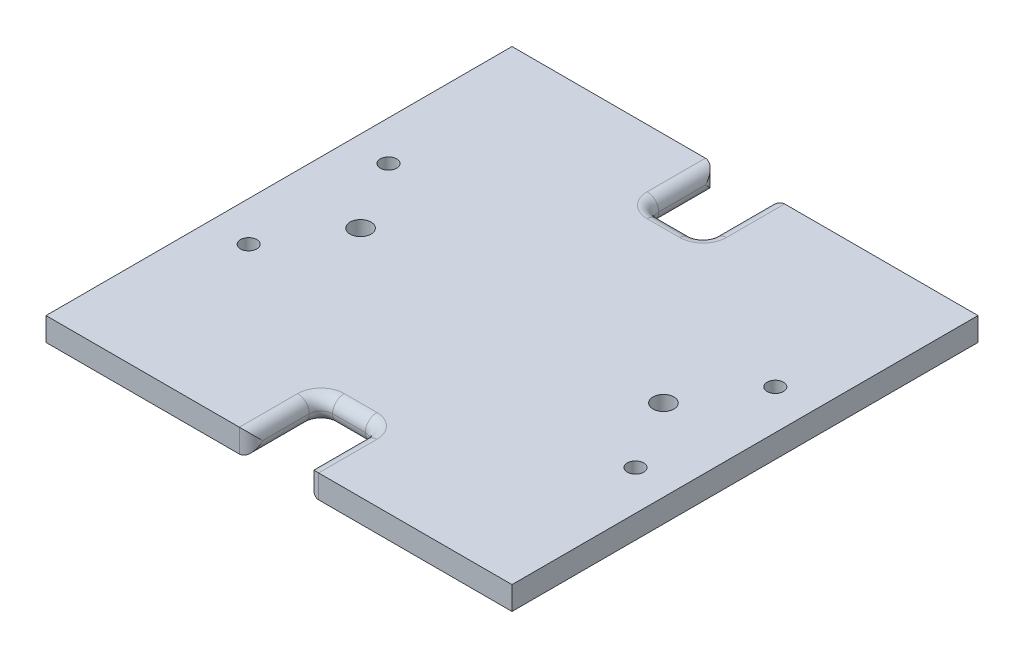
SolidWorks part; units mm, degrees
note: The reader was unsure of these and kept them because the rebuilt part matched: shared geometry of "Sketch4<4>", "Sketch4<6>".
ref_plane "Ön Düzlem" through (0, 0, 0) normal (0, 0, 1) x (1, 0, 0)
ref_plane "Üst Düzlem" through (0, 0, 0) normal (0, 1, 0) x (1, 0, 0)
ref_plane "Sağ Düzlem" through (0, 0, 0) normal (1, 0, 0) x (0, 0, -1)
sketch "Sketch1" plane through (0, 0, 0) normal (0, 0, 1) x (1, 0, 0)
  line L1 (-15.6006, 140) -> (-10.6006, 140)
  line L2 (-15.6006, 140) -> (-15.6006, 0)
  line L3 (-15.6006, 0) -> (-10.6006, 0)
  line L4 (-10.6006, 140) -> (-10.6006, 0)
  line L5 (-15.6006, 140) -> (-10.6006, 0) construction
  line L6 (-15.6006, 0) -> (-10.6006, 140) construction
  line L7 (-15.6006, 0) -> (94.3994, 0)
  line L8 (-15.6006, 0) -> (-15.6006, -5)
  line L9 (-15.6006, -5) -> (94.3994, -5)
  line L10 (94.3994, 0) -> (94.3994, -5)
  line L11 (94.3994, 0) -> (89.3994, 0)
  line L12 (94.3994, 0) -> (94.3994, 140)
  line L13 (94.3994, 140) -> (89.3994, 140)
  line L14 (89.3994, 0) -> (89.3994, 140)
  point P0 (-13.1006, 70)
  dimension "D1" = 5
  dimension "D2" = 140
  dimension "D3" = 5
  dimension "D4" = 110
  dimension "D5" = 5
extrude "Boss-Extrude1" add sketch "Sketch1" against normal blind 100 contours L10 L7 L3 L8 L9 | L14 L7 L12 L13
sketch "Sketch4" plane through (89.3994, 0, 0) normal (-1, 0, 0) x (0, 0, 1)
  line L0 (0, 0) -> (0, 45)
  line L1 (0, 0) -> (0, 140) construction
  line L2 (0, 45) -> (-100, 45)
  line L3 (-100, 0) -> (-100, 140) construction
  line L4 (-50, 45) -> (-82.05, 45)
  line L5 (-50, 45) -> (-17.95, 45)
  circle A0 centre (-50, 45) radius 9.85
  circle A1 centre (-82.05, 45) radius 9.85
  circle A2 centre (-17.95, 45) radius 9.85
  circle A3 centre (-82.05, 45) radius 7
  circle A4 centre (-50, 45) radius 7
  circle A5 centre (-17.95, 45) radius 7
  dimension "D4" = 19.7
  dimension "D5" = 19.7
  dimension "D6" = 19.7
  dimension "D7" = 14
  dimension "D8" = 14
  dimension "D9" = 14
  dimension "D1" = 45
  dimension "D2" = 32.05
  dimension "D3" = 32.05
extrude "Cut-Extrude3" cut sketch "Sketch4" along normal through all both and the other way through all contours L2 A3 L4 | L4 A3 L2 | L2 A4 | L2 A4 | L2 A5 | L2 A5
extrude "Cut-Extrude4" cut sketch "Sketch4<4>" against normal blind 3
sketch "Sketch4<4>" plane through (89.3994, 0, 0) normal (-1, 0, 0) x (0, 0, 1) same geometry as "Sketch4"
extrude "Cut-Extrude5" cut sketch "Sketch4<6>" along normal blind 103
sketch "Sketch4<6>" plane through (89.3994, 0, 0) normal (-1, 0, 0) x (0, 0, 1) same geometry as "Sketch4"
sketch "Sketch5" plane through (-15.6006, 0, 0) normal (-1, 0, 0) x (0, 0, 1)
  line L0 (0, 140) -> (0, 119.5)
  line L1 (0, 140) -> (0, -5) construction
  line L2 (0, 119.5) -> (-21.25, 119.5)
  line L3 (-100, 140) -> (-100, 119.5)
  line L4 (-100, 140) -> (-100, -5) construction
  line L5 (-100, 119.5) -> (-78.75, 119.5)
  circle A0 centre (-78.75, 119.5) radius 2.25
  circle A1 centre (-21.25, 119.5) radius 2.25
  dimension "D4" = 4.5
  dimension "D5" = 4.5
  dimension "D1" = 20.5
  dimension "D2" = 21.25
  dimension "D3" = 21.25
extrude "Cut-Extrude6" cut sketch "Sketch5" against normal up to next and the other way through all
sketch "Sketch6" plane through (0, -5, 0) normal (0, -1, 0) x (1, 0, 0)
  line L0 (39.3994, -50) -> (71.8994, -50)
  line L1 (39.3994, -50) -> (6.8994, -50)
  circle A0 centre (71.8994, -50) radius 2.25
  circle A1 centre (6.8994, -50) radius 2.25
  dimension "D3" = 4.5
  dimension "D4" = 4.5
  dimension "D1" = 32.5
  dimension "D2" = 32.5
extrude "Cut-Extrude7" cut sketch "Sketch6" against normal up to next
sketch "Sketch7" plane through (0, 0, 0) normal (0, 1, 0) x (1, 0, 0)
  line L0 (39.3994, 100) -> (33.3994, 100)
  line L1 (-10.6006, 100) -> (89.3994, 100) construction
  line L2 (33.3994, 100) -> (45.3994, 100)
  line L3 (9.1494, 50) -> (69.6494, 50)
  line L4 (33.3994, 100) -> (45.3994, 100)
  line L5 (33.3994, 100) -> (33.3994, 85)
  line L6 (33.3994, 85) -> (45.3994, 85)
  line L7 (45.3994, 100) -> (45.3994, 85)
  line L8 (33.3994, 0) -> (45.3994, 0)
  line L9 (33.3994, 15) -> (45.3994, 15)
  line L10 (45.3994, 0) -> (45.3994, 15)
  line L11 (33.3994, 0) -> (33.3994, 15)
  circle A0 centre (6.8994, 50) radius 2.25 construction
  circle A1 centre (71.8994, 50) radius 2.25 construction
  line M10 (-10.6006, 0) -> (89.3994, 0)
  line M12 (89.3994, 100) -> (-10.6006, 100)
  dimension "D1" = 6
  dimension "D2" = 12
  dimension "D3" = 15
extrude "Cut-Extrude8" cut sketch "Sketch7" against normal through all contours L7 L5 L6 M12 | L11 L10 L9 M10
fillet "Fillet3" radius 2.5 8 edges at (45.3994, -2.5, 0) (45.3994, -5, -7.5) (45.3994, 0, -7.5) (39.3994, -5, -15) (39.3994, 0, -15) (33.3994, -5, -7.5) (33.3994, -2.5, 0) (33.3994, 0, -7.5)
fillet "Fillet4" radius 2.5 8 edges at (33.3994, -2.5, -100) (33.3994, -5, -92.5) (33.3994, 0, -92.5) (39.3994, -5, -85) (39.3994, 0, -85) (45.3994, -5, -92.5) (45.3994, -2.5, -100) (45.3994, 0, -92.5)
fillet "Fillet6" radius 5 4 edges at (-13.1006, 140, -100) (-13.1006, 140, 0) (91.8994, 140, -100) (91.8994, 140, 0)
sketch "Sketch8" plane through (0, 0, 0) normal (0, 1, 0) x (1, 0, 0)
  line L1 (-15.6006, 100) -> (-10.6006, 100)
  line L2 (-15.6006, 100) -> (-15.6006, 0)
  line L3 (-15.6006, 0) -> (-10.6006, 0)
  line L4 (-10.6006, 100) -> (-10.6006, 0)
  line L5 (89.3994, 100) -> (94.3994, 100)
  line L6 (89.3994, 100) -> (89.3994, 0)
  line L7 (89.3994, 0) -> (94.3994, 0)
  line L8 (94.3994, 100) -> (94.3994, 0)
extrude "Cut-Extrude9" cut sketch "Sketch8" against normal through all both and the other way through all
sketch "Sketch11" plane through (0, 0, 0) normal (0, 1, 0) x (1, 0, 0)
  line L0 (89.3994, 50) -> (80.8994, 50)
  line L1 (89.3994, 100) -> (89.3994, 0) construction
  line L2 (39.3994, 82.5) -> (39.3994, 17.5)
  line L3 (80.8994, 35) -> (80.8994, 65)
  line L4 (42.8994, 82.5) -> (35.8994, 82.5) construction
  line L5 (35.8994, 17.5) -> (42.8994, 17.5) construction
  circle A0 centre (80.8994, 65) radius 1.75
  circle A1 centre (80.8994, 35) radius 1.75
  circle A2 centre (-2.1006, 35) radius 1.75
  circle A3 centre (-2.1006, 65) radius 1.75
  dimension "D2" = 3.5
  dimension "D4" = 3.5
  dimension "D1" = 8.5
  dimension "D3" = 30
extrude "Cut-Extrude10" cut sketch "Sketch11" against normal up to next
